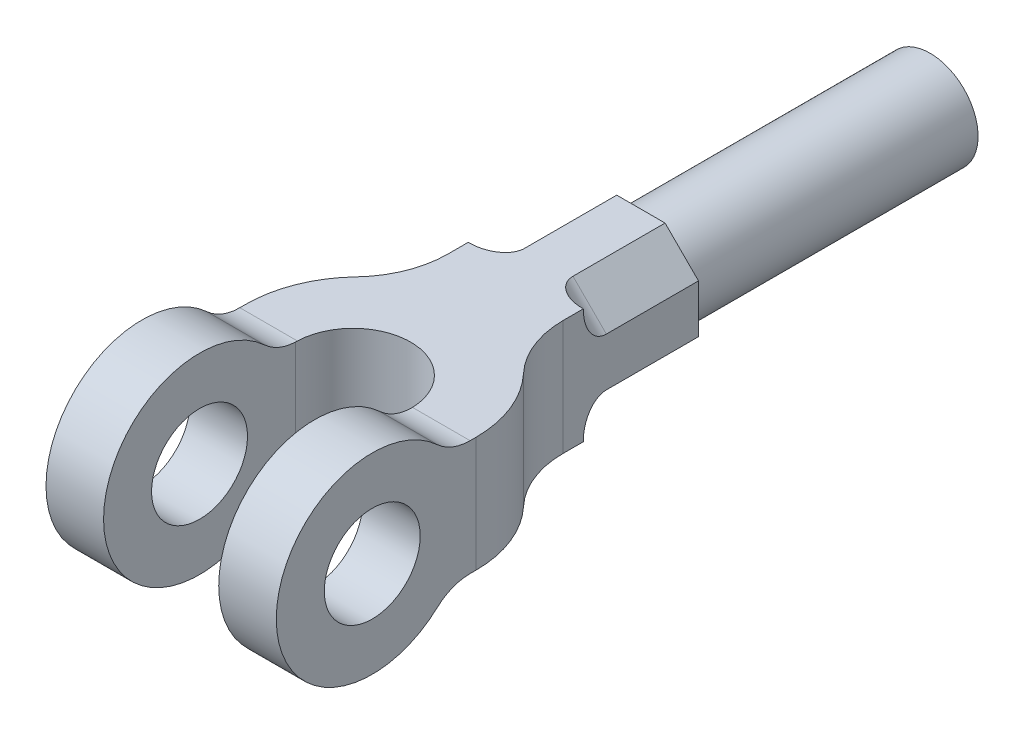
SolidWorks part; units mm, degrees
ref_plane "Front Plane" through (0, 0, 0) normal (0, 0, 1) x (1, 0, 0)
ref_plane "Top Plane" through (0, 0, 0) normal (0, 1, 0) x (1, 0, 0)
ref_plane "Right Plane" through (0, 0, 0) normal (1, 0, 0) x (0, 0, -1)
sketch "Sketch2" plane through (0, 0, 0) normal (0, 1, 0) x (1, 0, 0)
  line L1 (0, 0) -> (-1200, 0)
  line L2 (0, 0) -> (0, 2500)
  line L3 (0, 2500) -> (-1200, 2500)
  line L4 (-1200, 0) -> (-1200, 2500)
  dimension "D1" = 1200
  dimension "D2" = 2500
extrude "Boss-Extrude1" add sketch "Sketch2" along normal blind 1000
sketch "Sketch3" plane through (0, 1000, 0) normal (0, 1, 0) x (1, 0, 0)
  line L0 (-600, 2500) -> (-600, 0) construction
  line L1 (0, 2500) -> (-1200, 2500) construction
  line L2 (-1200, 0) -> (0, 0) construction
  line L3 (-900, 2500) -> (-900, 1794.9834)
  line L4 (-300, 2500) -> (-300, 1794.9834)
  line L5 (-900, 1000) -> (-900, 0)
  line L6 (-300, 1000) -> (-300, 0)
  arc A0 (-300, 1000) -> (-900, 1000) centre (-600, 1000) ccw
  arc A1 (-1036.3636, 1451.8092) -> (-163.6364, 1451.8092) centre (-600, 1040) ccw
  arc A2 (-300, 1794.9834) -> (-163.6364, 1451.8092) centre (200, 1794.9834) ccw
  arc A3 (-900, 1794.9834) -> (-1036.3636, 1451.8092) centre (-1400, 1794.9834) cw
  point P15 (-300, 1559.6152)
  point P18 (-900, 1559.6152)
  line M5 (0, 0) -> (0, 2500)
  line M6 (0, 2500) -> (-1200, 2500)
  line M7 (-1200, 2500) -> (-1200, 0)
  line M8 (-1200, 0) -> (0, 0)
  dimension "D1" = 600
  dimension "D2" = 1200
  dimension "D6" = 500
  dimension "D3" = 40
  dimension "D4" = 1500
  dimension "D5" = 300
extrude "Cut-Extrude4" cut sketch "Sketch3" against normal through all contours A3 L3 A1 M6 M7 | L4 A2 A1 M5 M6 region at (-1061.7481, 1000, -1955.027) region at (-138.2519, 1000, -1955.027)
extrude "Cut-Extrude5" cut sketch "Sketch3<4>" against normal through all contours L0 A0 L5 A1 | A0 L0 A1 L6 | A1 L0 L6 M8 | L0 A1 L5 M8 region at (-459.5149, 1000, -853.3741) region at (-740.4851, 1000, -853.3741) region at (-445.7522, 1000, -233.6195) region at (-754.2478, 1000, -233.6195)
sketch "Sketch3<4>" plane through (0, 1000, 0) normal (0, 1, 0) x (1, 0, 0) same geometry as "Sketch3"
sketch "Sketch4" plane through (0, 0, 0) normal (1, 0, 0) x (0, 0, -1)
  line L0 (0, 1000) -> (0, 0) construction
  line L1 (0, 0) -> (2500, 0) construction
  line L2 (500, 500) -> (2500, 500) construction
  line L3 (0, 1000) -> (1040, 1000) construction
  line L4 (2500, 0) -> (2500, 1000) construction
  line L5 (2500, 1000) -> (1794.9834, 1000) construction
  line L6 (2500, 800) -> (1009.902, 800)
  line L7 (2500, 800) -> (2500, 200)
  line L8 (2500, 200) -> (1009.902, 200)
  line L10 (1794.9834, 1000) -> (1451.8092, 1000) construction
  line L11 (1451.8092, 1000) -> (1040, 1000) construction
  line L12 (1000, 1000) -> (0, 1000) construction
  line L13 (0, 1000) -> (0, 0)
  line L14 (0, 0) -> (2500, 0)
  line L15 (2500, 0) -> (2500, 1000)
  line L16 (2500, 1000) -> (1794.9834, 1000)
  line L17 (1794.9834, 1000) -> (1451.8092, 1000)
  line L18 (1451.8092, 1000) -> (1040, 1000)
  line L19 (1000, 1000) -> (0, 1000)
  arc A0 (839.9346, 866.6667) -> (839.9346, 133.3333) centre (500, 500) ccw
  circle A1 centre (500, 500) radius 250
  arc A2 (1009.902, 200) -> (839.9346, 133.3333) centre (1009.902, -50) ccw
  arc A3 (1009.902, 800) -> (839.9346, 866.6667) centre (1009.902, 1050) cw
  line M2 (0, 0) -> (1040, 0)
  line M3 (1040, 0) -> (1040, 1000)
  line M4 (1040, 1000) -> (0, 1000)
  line M5 (0, 1000) -> (0, 0)
  dimension "D1" = 500
  dimension "D3" = 250
  dimension "D2" = 600
extrude "Cut-Extrude6" cut sketch "Sketch4" against normal through all contours L8 A2 A0 L14 M3 | A0 L19 M5 | A3 L6 A0 M3 M4 | L17 L18 L6 L15 L16 M3 | L14 L15 L8 M3 | A0 L13 M2 | A1 region at (0, 900, -1770) region at (0, 922.7719, -892.915) region at (0, 100, -1770) region at (0, 77.2281, -892.915) region at (0, 888.316, -111.684) region at (0, 111.684, -111.684) region at (0, 500, -500)
sketch "Sketch5" plane through (0, 0, -2500) normal (0, 0, -1) x (-1, 0, 0)
  line L0 (900, 800) -> (300, 200) construction
  line L1 (726, 800) -> (900, 626)
  line L2 (900, 800) -> (300, 800) construction
  line L3 (900, 200) -> (900, 800) construction
  line L4 (900, 626) -> (900, 800)
  line L5 (900, 800) -> (726, 800)
  line L6 (900, 374) -> (726, 200)
  line L7 (474, 200) -> (300, 374)
  line L8 (300, 626) -> (474, 800)
  circle A0 centre (600, 500) radius 250
  point P21 (600, 500)
  line M3 (900, 800) -> (300, 800)
  line M4 (300, 800) -> (300, 200)
  line M5 (300, 200) -> (900, 200)
  line M6 (900, 200) -> (900, 800)
  dimension "D1" = 500
  dimension "D2" = 174
  dimension "D3" = 174
  dimension "D4" = 4
extrude "Cut-Extrude7" cut sketch "Sketch5" against normal blind 600 contours L8 M4 M3 | L7 L0 M5 | L6 M6 M5 | L0 L1 M3 | L0 L1 M6 | L0 L7 M4 region at (-871, 713, -2500) region at (-813, 771, -2500) region at (-842, 258, -2500) region at (-358, 742, -2500) region at (-387, 229, -2500) region at (-329, 287, -2500)
extrude "Boss-Extrude2" add sketch "Sketch5<3>" along normal blind 1507 contours L0 A0 | A0 L0 region at (-675.0264, 424.9736, -2500) region at (-524.9736, 575.0264, -2500)
sketch "Sketch5<3>" plane through (0, 0, -2500) normal (0, 0, -1) x (-1, 0, 0) same geometry as "Sketch5"
fillet "Fillet2" radius 120 1 edges at (-387, 713, -1900) type face fillet first side face at (-358, 742, -1900) second side face at (-387, 713, -2200)
fillet "Fillet3" radius 120 1 edges at (-387, 287, -1900) type face fillet first side face at (-358, 258, -1900) second side face at (-387, 287, -2200)
fillet "Fillet4" radius 120 1 edges at (-813, 713, -1900) type face fillet first side face at (-842, 742, -1900) second side face at (-813, 713, -2200)
fillet "Fillet5" radius 120 1 edges at (-813, 287, -1900) type face fillet first side face at (-842, 258, -1900) second side face at (-813, 287, -2200)
